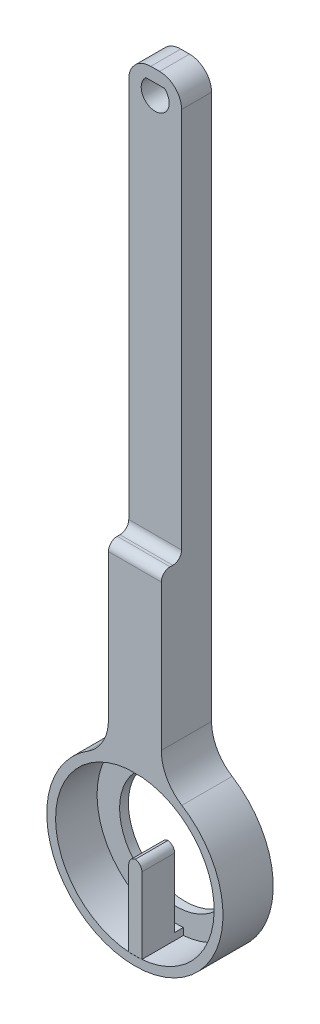
SolidWorks part; units mm, degrees
ref_plane "Front Plane" through (0, 0, 0) normal (0, 0, 1) x (1, 0, 0)
ref_plane "Top Plane" through (0, 0, 0) normal (0, 1, 0) x (1, 0, 0)
ref_plane "Right Plane" through (0, 0, 0) normal (1, 0, 0) x (0, 0, -1)
sketch "Sketch1" plane through (0, 0, 0) normal (0, 0, 1) x (1, 0, 0)
  line L1 (-4, -87.5) -> (4, -87.5)
  line L2 (-4, -87.5) -> (-4, 87.5)
  line L3 (-4, 87.5) -> (4, 87.5)
  line L4 (4, -87.5) -> (4, 87.5)
  line L5 (-4, -87.5) -> (4, 87.5) construction
  line L6 (-4, 87.5) -> (4, -87.5) construction
  circle A0 centre (0, 87.5) radius 4
  circle A1 centre (0, -87.5) radius 20
  point P0 (0, 0)
  dimension "D1" = 8
  dimension "D2" = 175
extrude "Boss-Extrude1" add sketch "Sketch1" along normal blind 13 contours A1 L4 A0 L2 | L2 A1 L4 L1 | L3 A0 | L3 A0 region at (0, -88.9381, 0) region at (0, 8.3647, 0) region at (0, 89.1977, 0) region at (0, 85.8023, 0)
extrude "Boss-Extrude2" add sketch "Sketch1<3>" along normal blind 13 contours L4 A1 L2 L1 region at (0, -77.5667, 0)
sketch "Sketch1<3>" plane through (0, 0, 0) normal (0, 0, 1) x (1, 0, 0) same geometry as "Sketch1"
sketch "Sketch2" plane through (0, 0, 13) normal (0, 0, 1) x (1, 0, 0)
  line L0 (-4, 87.5) -> (4, 87.5) construction
  line L1 (0, 84.375) -> (0, 89.875) construction
  line L2 (-1.8367, 90.0283) -> (1.8367, 90.0283)
  circle A0 centre (0, 87.5) radius 3.125
  circle A1 centre (0, 62.5) radius 3.125
  point P12 (0, 89.875)
  point P13 (0, 90.0283)
  dimension "D1" = 5.5
  dimension "D2" = 2
extrude "Cut-Extrude1" cut sketch "Sketch2" against normal blind 13 contours A0 region at (0, 87.3585, 13)
sketch "Sketch3" plane through (4, 0, 0) normal (1, 0, 0) x (0, 0, -1)
  line L1 (-13, 91.5) -> (-6.3732, 91.5)
  line L2 (-13, 91.5) -> (-13, 72.0797)
  line L3 (-13, 72.0797) -> (-6.3732, 72.0797)
  line L4 (-6.3732, 91.5) -> (-6.3732, 72.0797)
extrude "Cut-Extrude2" cut sketch "Sketch3" against normal blind 13
fillet "Fillet1" radius 10 1 edges at (0, 72.0797, 6.3732)
sketch "Sketch4" plane through (0, 0, 13) normal (0, 0, 1) x (1, 0, 0)
  line L0 (-20, -87.5) -> (20, -87.5) construction
  line L1 (0, -107.5) -> (0, -69.6414) construction
  arc A0 (-4, -67.9041) -> (4, -67.9041) centre (0, -87.5) ccw construction
  circle A1 centre (0, -87.5) radius 20
extrude "Boss-Extrude3" add sketch "Sketch4" along normal blind 13
sketch "Sketch5" plane through (4, 0, 0) normal (1, 0, 0) x (0, 0, -1)
  line L0 (-13, -67.9041) -> (-13, 72.0797) construction
  line L1 (-13, 61.0572) -> (-13, 87.5)
  line L2 (-13, 87.5) -> (-6.3732, 87.5)
  arc A0 (-6.3732, 87.5) -> (-13, 61.0572) centre (-49.1244, 84.1621) cw
extrude "Cut-Extrude3" cut sketch "Sketch5" against normal blind 13
sketch "Sketch6" plane through (0, 0, 26) normal (0, 0, 1) x (1, 0, 0)
  circle A0 centre (0, -87.5) radius 18
extrude "Cut-Extrude4" cut sketch "Sketch6" against normal blind 24
sketch "Sketch8" plane through (0, 0, 2) normal (0, 0, 1) x (1, 0, 0)
  line L0 (-1.3907, -105.4462) -> (-1.3907, -86.4462)
  line L1 (1.6093, -86.4462) -> (1.6093, -105.4279)
  line L2 (-1.3907, -86.4462) -> (1.6093, -86.4462)
  line L3 (-1.3907, -105.4462) -> (1.6093, -105.4279)
  line L4 (17.1093, -101.2315) -> (17.1093, -73.7685)
  line L5 (-16.8907, -100.8575) -> (-16.8907, -74.1425)
  circle A0 centre (0, -87.5) radius 18 construction
  point P9 (17.1093, -87.5)
  point P12 (-16.8907, -87.5)
  dimension "D1" = 3
  dimension "D2" = 19
  dimension "D3" = 15.5
  dimension "D4" = 15.5
extrude "Boss-Extrude7" add sketch "Sketch8" along normal blind 22 separate body contours L3 L1 L2 L0
fillet "Fillet5" radius 1.75 2 edges at (1.6093, -86.4462, 13) (-1.3907, -86.4462, 13)
fillet "Fillet6" radius 20 1 edges at (0, 61.0572, 13)
sketch "Sketch13" plane through (-4, 0, 0) normal (-1, 0, 0) x (0, 0, 1)
  line L0 (6.3732, 87.5) -> (6.3732, 3.1735)
  line L1 (6.3732, 3.1735) -> (13, 3.1735)
  line L2 (13, -67.9041) -> (13, 55.8052) construction
  line L3 (13, 3.1735) -> (13, 87.5)
  line L4 (13, 87.5) -> (6.3732, 87.5)
extrude "Cut-Extrude8" cut sketch "Sketch13" against normal blind 22
fillet "Fillet8" radius 21.5 1 edges at (0, 3.1735, 6.3732)
fillet "Fillet9" radius 21.5 1 edges at (0, 3.1735, 13)
sketch "Sketch14" plane through (-4, 0, 0) normal (-1, 0, 0) x (0, 0, 1)
  line L1 (6.3732, -28.0179) -> (23.434, -28.0179)
  line L2 (6.3732, -28.0179) -> (6.3732, 18.6989)
  line L3 (6.3732, 18.6989) -> (23.434, 18.6989)
  line L4 (23.434, -28.0179) -> (23.434, 18.6989)
extrude "Cut-Extrude10" cut sketch "Sketch14" against normal blind 22
sketch "Sketch23" plane through (0, 0, 0) normal (0, 0, -1) x (-1, 0, 0)
  circle A0 centre (0, -87.5) radius 16.3958
extrude "Cut-Extrude14" cut sketch "Sketch23" against normal blind 4
sketch "Sketch24" plane through (0, 0, 0) normal (0, 0, -1) x (-1, 0, 0)
  arc A0 (0, -71.1042) -> (0, -103.8958) centre (0, -87.5) ccw
  circle A1 centre (0, -87.5) radius 16.3958 construction
  arc A2 (0, -71.1042) -> (0, -103.8958) centre (0, -87.5) cw
  arc A3 (0, -74.7441) -> (0, -100.5129) centre (0, -87.6285) cw
  arc A4 (0, -74.7441) -> (0, -100.5129) centre (0, -87.6285) ccw
extrude "Boss-Extrude16" add sketch "Sketch24" against normal blind 2
sketch "Sketch25" plane through (0, 0, 26) normal (0, 0, 1) x (1, 0, 0)
  circle A0 centre (0, -87.6285) radius 20.1285
extrude "Cut-Extrude15" cut sketch "Sketch25" against normal blind 9
sketch "Sketch26" plane through (0, 0, 6.3732) normal (0, 0, 1) x (1, 0, 0)
  line L0 (-4, 80.8242) -> (-4, -28.0179) construction
  line L1 (-4, 66.3734) -> (4.8485, 66.3734)
  line L2 (-4, 66.3734) -> (-4, 92.3734)
  line L3 (-4, 92.3734) -> (4.8485, 92.3734)
  line L4 (4.8485, 66.3734) -> (4.8485, 92.3734)
  dimension "D1" = 26
extrude "Cut-Extrude16" cut sketch "Sketch26" against normal blind 9 contours L2 L1 L4 L3
sketch "Sketch27" plane through (0, 0, 6.3732) normal (0, 0, 1) x (1, 0, 0)
  line L0 (0, 58.1905) -> (0, 63.6905) construction
  line L1 (-2.1323, 63.8405) -> (2.1323, 63.8405)
  circle A0 centre (0, 61.4179) radius 3.2274
  dimension "D1" = 5.5
  dimension "D2" = 0.15
extrude "Cut-Extrude17" cut sketch "Sketch27" against normal blind 9 contours L1 A0 region at (0, 61.2051, 6.3732)
fillet "Fillet21" radius 3.5 2 edges at (4, 66.3734, 3.1866) (-4, 66.3734, 3.1866)
sketch "Sketch28" plane through (0, 0, 0) normal (0, 0, -1) x (-1, 0, 0)
  line L3 (-6, -69.5886) -> (6, -69.5886)
  line L4 (-6, -69.5886) -> (-6, -27.0166)
  line L5 (-6, -27.0166) -> (6, -27.0166)
  line L6 (6, -69.5886) -> (6, -27.0166)
  arc A0 (-2.1323, 63.8405) -> (2.1323, 63.8405) centre (0, 61.4179) ccw construction
  dimension "D1" = 12
  dimension "D2" = 6
extrude "Boss-Extrude20" add sketch "Sketch28" against normal blind 15.8
sketch "Sketch30" plane through (0, 0, 0) normal (0, 0, -1) x (-1, 0, 0)
  line L0 (2.1323, 63.8405) -> (-2.1323, 63.8405) construction
  line L1 (2.1323, 63.8405) -> (-2.1323, 63.8405)
  line L3 (-6, -27.0166) -> (6, -27.0166)
  line L4 (-6, -27.0166) -> (-6, 66.5832)
  line L5 (-6, 66.5832) -> (6, 66.5832)
  line L6 (6, -27.0166) -> (6, 66.5832)
  arc A0 (-2.1323, 63.8405) -> (2.1323, 63.8405) centre (0, 61.4179) ccw construction
  arc A1 (-2.1323, 63.8405) -> (2.1323, 63.8405) centre (0, 61.4179) ccw
  dimension "D1" = 12
extrude "Boss-Extrude21" add sketch "Sketch30" against normal blind 6.8
fillet "Fillet23" radius 5 2 edges at (6, 66.5832, 3.4) (-6, 66.5832, 3.4)
sketch "Sketch33" plane through (0, 0, 6.8) normal (0, 0, 1) x (1, 0, 0)
  line L0 (-2.0993, 63.803) -> (2.0993, 63.803)
  line L1 (-2.1323, 63.8405) -> (2.1323, 63.8405) construction
  line L2 (-2.1323, 63.8405) -> (2.1323, 63.8405)
  arc A0 (-2.1323, 63.8405) -> (2.1323, 63.8405) centre (0, 61.4179) ccw construction
  arc A1 (-2.1323, 63.8405) -> (2.1323, 63.8405) centre (0, 61.4179) ccw
  arc A2 (-2.0993, 63.803) -> (2.0993, 63.803) centre (0, 61.4179) ccw
extrude "Boss-Extrude22" add sketch "Sketch33" against normal blind 6.8
sketch "Sketch34" plane through (-6, 0, 0) normal (-1, 0, 0) x (0, 0, 1)
  line L0 (0, -107.5) -> (17, -107.5) construction
  line L1 (11.4141, -27.0166) -> (17, -27.0166)
  line L2 (11.4141, -27.0166) -> (11.4141, -107.5)
  line L3 (11.4141, -107.5) -> (17, -107.5)
  line L4 (17, -27.0166) -> (17, -107.5)
extrude "Cut-Extrude18" cut sketch "Sketch34" against normal blind 41 and the other way blind 29
fillet "Fillet27" radius 2 2 edges at (0, -27.0166, 6.8) (0, -27.0166, 11.4141)
fillet "Fillet28" radius 10 2 edges at (-6, -68.4212, 5.707) (6, -68.4212, 5.707)
